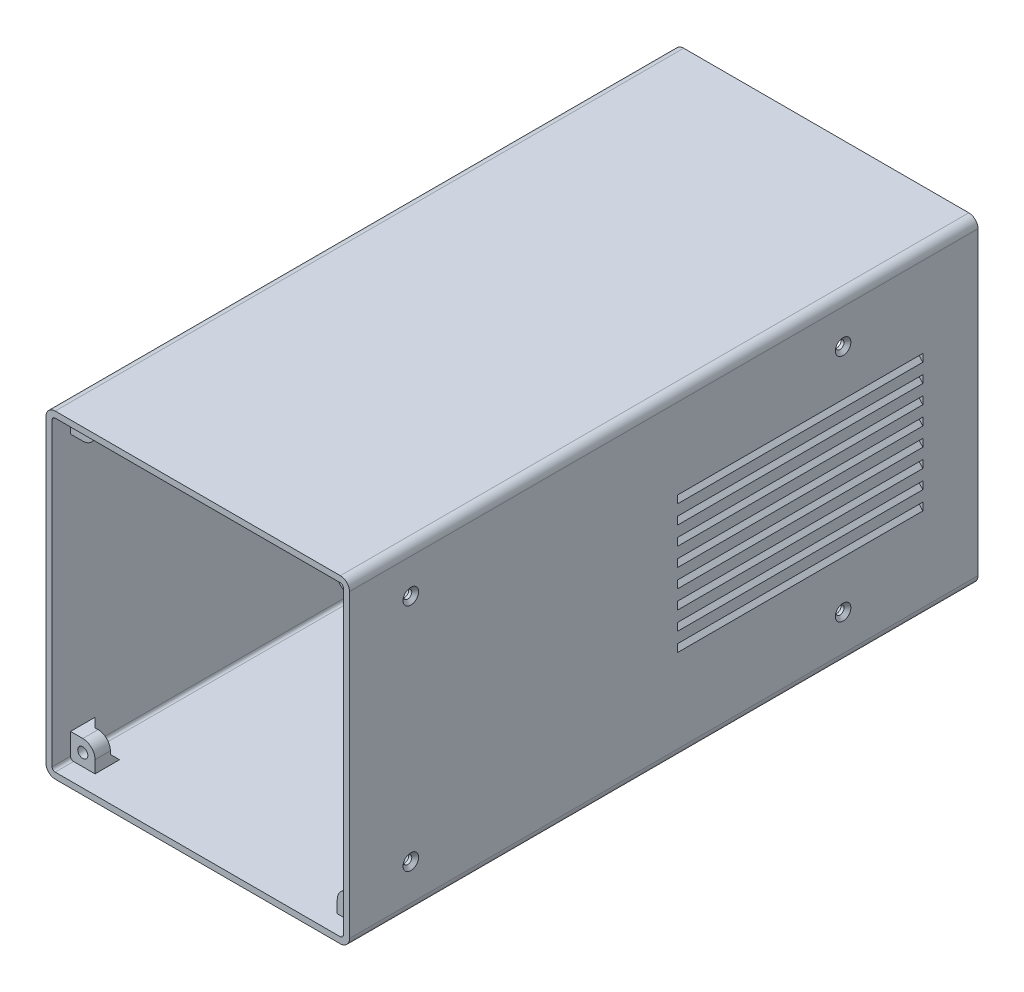
SolidWorks part; units mm, degrees
ref_plane "前视基准面" through (0, 0, 0) normal (0, 0, 1) x (1, 0, 0)
ref_plane "上视基准面" through (0, 0, 0) normal (0, 1, 0) x (1, 0, 0)
ref_plane "右视基准面" through (0, 0, 0) normal (1, 0, 0) x (0, 0, -1)
sketch "草图1" plane through (0, 0, 0) normal (0, 0, 1) x (1, 0, 0)
  line L1 (-46.5, -50) -> (46.5, -50)
  line L2 (-47.5, -49) -> (-47.5, 49)
  line L3 (-46.5, 50) -> (46.5, 50)
  line L4 (47.5, -49) -> (47.5, 49)
  line L5 (-47.5, -50) -> (47.5, 50) construction
  line L6 (-47.5, 50) -> (47.5, -50) construction
  arc A0 (-46.5, -50) -> (-47.5, -49) centre (-46.5, -49) cw
  arc A1 (46.5, -50) -> (47.5, -49) centre (46.5, -49) ccw
  arc A2 (46.5, 50) -> (47.5, 49) centre (46.5, 49) cw
  arc A3 (-47.5, 49) -> (-46.5, 50) centre (-46.5, 49) cw
  point P0 (0, 0)
  dimension "D3" = 1
  dimension "D1" = 100
  dimension "D2" = 95
extrude "凸台-拉伸1" add sketch "草图1" along normal blind 205
shell "抽壳1" thickness 2 removed face at (0, 0, 205) removed face at (0, 0, 0) outward yes
ref_plane "基准面2" through (0, 0, 6) normal (0, 0, -1) x (-1, 0, 0)
ref_plane "基准面3" through (0, 0, 199) normal (0, 0, 1) x (1, 0, 0)
sketch "草图6" plane through (0, 0, 6) normal (0, 0, -1) x (-1, 0, 0)
  line L0 (0, 0) -> (0, 33.2854) construction
  line L1 (-43.5, 42) -> (-47.5, 42)
  line L2 (-39.5, 46) -> (-39.5, 50)
  line L3 (-39.5, 50) -> (-47.5, 50)
  line L4 (-47.5, 42) -> (-47.5, 50)
  line L5 (0, 0) -> (27.226, 0) construction
  line L6 (-46.5, 50) -> (46.5, 50) construction
  line L7 (-47.5, -49) -> (-47.5, 49) construction
  line L8 (39.5, 46) -> (39.5, 50)
  line L9 (43.5, 42) -> (47.5, 42)
  line L10 (47.5, 42) -> (47.5, 50)
  line L11 (39.5, 50) -> (47.5, 50)
  line L12 (39.5, -50) -> (47.5, -50)
  line L13 (47.5, -42) -> (47.5, -50)
  line L14 (43.5, -42) -> (47.5, -42)
  line L15 (39.5, -46) -> (39.5, -50)
  line L16 (-47.5, -42) -> (-47.5, -50)
  line L17 (-39.5, -50) -> (-47.5, -50)
  line L18 (-39.5, -46) -> (-39.5, -50)
  line L19 (-43.5, -42) -> (-47.5, -42)
  arc A0 (-43.5, 42) -> (-39.5, 46) centre (-43.5, 46) ccw
  circle A1 centre (-43.5, 46) radius 1.65
  circle A2 centre (43.5, 46) radius 1.65
  arc A3 (43.5, 42) -> (39.5, 46) centre (43.5, 46) cw
  arc A4 (43.5, -42) -> (39.5, -46) centre (43.5, -46) ccw
  circle A5 centre (43.5, -46) radius 1.65
  circle A6 centre (-43.5, -46) radius 1.65
  arc A7 (-43.5, -42) -> (-39.5, -46) centre (-43.5, -46) cw
  point P15 (-39.5, 42)
  dimension "D3" = 4
  dimension "D4" = 3.3
  dimension "D1" = 8
  dimension "D2" = 8
extrude "凸台-拉伸2" add sketch "草图6" against normal blind 5
sketch "草图7" plane through (0, 0, 199) normal (0, 0, 1) x (1, 0, 0)
  line L0 (-46.5, -50) -> (-39.5, -50) construction
  line L1 (-39.5, -50) -> (-39.5, -46) construction
  line L2 (-43.5, -42) -> (-47.5, -42) construction
  line L3 (-47.5, -42) -> (-47.5, -49) construction
  line L4 (39.5, -50) -> (46.5, -50) construction
  line L5 (47.5, -49) -> (47.5, -42) construction
  line L6 (47.5, -42) -> (43.5, -42) construction
  line L7 (39.5, -46) -> (39.5, -50) construction
  line L8 (46.5, 50) -> (39.5, 50) construction
  line L9 (39.5, 50) -> (39.5, 46) construction
  line L10 (43.5, 42) -> (47.5, 42) construction
  line L11 (47.5, 42) -> (47.5, 49) construction
  line L12 (-39.5, 50) -> (-46.5, 50) construction
  line L13 (-47.5, 49) -> (-47.5, 42) construction
  line L14 (-47.5, 42) -> (-43.5, 42) construction
  line L15 (-39.5, 46) -> (-39.5, 50) construction
  line L16 (-46.5, -50) -> (-39.5, -50)
  line L17 (-39.5, -50) -> (-39.5, -46)
  line L18 (-43.5, -42) -> (-47.5, -42)
  line L19 (-47.5, -42) -> (-47.5, -49)
  line L20 (39.5, -50) -> (46.5, -50)
  line L21 (47.5, -49) -> (47.5, -42)
  line L22 (47.5, -42) -> (43.5, -42)
  line L23 (39.5, -46) -> (39.5, -50)
  line L24 (46.5, 50) -> (39.5, 50)
  line L25 (39.5, 50) -> (39.5, 46)
  line L26 (43.5, 42) -> (47.5, 42)
  line L27 (47.5, 42) -> (47.5, 49)
  line L28 (-39.5, 50) -> (-46.5, 50)
  line L29 (-47.5, 49) -> (-47.5, 42)
  line L30 (-47.5, 42) -> (-43.5, 42)
  line L31 (-39.5, 46) -> (-39.5, 50)
  arc A0 (-47.5, -49) -> (-46.5, -50) centre (-46.5, -49) ccw construction
  arc A1 (-39.5, -46) -> (-43.5, -42) centre (-43.5, -46) ccw construction
  arc A2 (46.5, -50) -> (47.5, -49) centre (46.5, -49) ccw construction
  arc A3 (43.5, -42) -> (39.5, -46) centre (43.5, -46) ccw construction
  arc A4 (47.5, 49) -> (46.5, 50) centre (46.5, 49) ccw construction
  arc A5 (39.5, 46) -> (43.5, 42) centre (43.5, 46) ccw construction
  arc A6 (-46.5, 50) -> (-47.5, 49) centre (-46.5, 49) ccw construction
  arc A7 (-43.5, 42) -> (-39.5, 46) centre (-43.5, 46) ccw construction
  circle A8 centre (43.5, -46) radius 1.65 construction
  circle A9 centre (43.5, 46) radius 1.65 construction
  circle A10 centre (-43.5, 46) radius 1.65 construction
  circle A11 centre (-43.5, -46) radius 1.65 construction
  arc A12 (-47.5, -49) -> (-46.5, -50) centre (-46.5, -49) ccw
  arc A13 (-39.5, -46) -> (-43.5, -42) centre (-43.5, -46) ccw
  arc A14 (46.5, -50) -> (47.5, -49) centre (46.5, -49) ccw
  arc A15 (43.5, -42) -> (39.5, -46) centre (43.5, -46) ccw
  arc A16 (47.5, 49) -> (46.5, 50) centre (46.5, 49) ccw
  arc A17 (39.5, 46) -> (43.5, 42) centre (43.5, 46) ccw
  arc A18 (-46.5, 50) -> (-47.5, 49) centre (-46.5, 49) ccw
  arc A19 (-43.5, 42) -> (-39.5, 46) centre (-43.5, 46) ccw
  circle A20 centre (43.5, -46) radius 1.65
  circle A21 centre (43.5, 46) radius 1.65
  circle A22 centre (-43.5, 46) radius 1.65
  circle A23 centre (-43.5, -46) radius 1.65
extrude "凸台-拉伸3" add sketch "草图7" against normal blind 5
sketch "草图8" plane through (-49.5, 0, 0) normal (-1, 0, 0) x (0, 0, 1)
  line L0 (0, 49) -> (0, -49) construction
  line L1 (96, -43) -> (32, -43) construction
  line L2 (96, -43) -> (96, 43) construction
  line L3 (96, 43) -> (32, 43) construction
  line L4 (32, -43) -> (32, 43) construction
  line L5 (96, -43) -> (32, 43) construction
  line L6 (96, 43) -> (32, -43) construction
  line L7 (100, -46.5) -> (28, -46.5) construction
  line L8 (100, -46.5) -> (100, 46.5) construction
  line L9 (100, 46.5) -> (28, 46.5) construction
  line L10 (28, -46.5) -> (28, 46.5) construction
  line L11 (100, -46.5) -> (28, 46.5) construction
  line L12 (100, 46.5) -> (28, -46.5) construction
  point P0 (64, 0)
  point P5 (64, 0)
  dimension "D1" = 72
  dimension "D2" = 93
  dimension "D3" = 86
  dimension "D4" = 64
  dimension "D5" = 28
hole_wizard "#3 平头机械螺钉的锥形沉头孔 (100)1" positions "草图9" profile "草图10" countersink size "#3" standard "ANSI Inch" end condition up to next
sketch "草图9" plane through (-49.5, 0, 0) normal (-1, 0, 0) x (0, 0, 1)
  point P0 (32, 43)
  point P3 (96, 43)
  point P6 (96, -43)
  point P9 (32, -43)
sketch "草图10" plane through (-49.5, 43, 32) normal (0, 1, 0) x (0, 0, 1)
  line L0 (0, 0) -> (0, 2)
  line L1 (0, 2) -> (1.3208, 2)
  line L2 (1.3208, 2) -> (1.3208, 1.0124)
  line L3 (1.3208, 1.0124) -> (2.5273, 0)
  line L5 (2.5273, 0) -> (0, 0)
  line L6 (-1.3208, 1.0124) -> (-2.5273, 0) construction
  line L11 (0, -6.35) -> (0, 107.95) construction
  dimension "通孔孔直径" = 2.6416
  dimension "通孔孔深度" = 2
  dimension "近端锥形沉头孔直径" = 5.0546
  dimension "近端锥形沉头孔角度" = 100
sketch "草图11" plane through (49.5, 0, 0) normal (1, 0, 0) x (0, 0, -1)
  line L0 (0, -49) -> (0, 49) construction
  line L1 (-40, -46) -> (-190, -46) construction
  line L2 (-40, -46) -> (-40, 46) construction
  line L3 (-40, 46) -> (-190, 46) construction
  line L4 (-190, -46) -> (-190, 46) construction
  line L13 (-194, 50) -> (-11, 50) construction
  line L15 (-185, 37.7) -> (-44, 37.7) construction
  line L16 (-185, 37.7) -> (-185, -37.3) construction
  line L17 (-185, -37.3) -> (-44, -37.3) construction
  line L18 (-44, 37.7) -> (-44, -37.3) construction
  dimension "D1" = 150
  dimension "D2" = 92
  dimension "D3" = 40
  dimension "D4" = 8.7
  dimension "D5" = 4
  dimension "D11" = 4
  dimension "D12" = 141
  dimension "D13" = 75
hole_wizard "#3 平头机械螺钉的锥形沉头孔 (100)2" positions "草图16" profile "草图17" countersink size "#3" standard "ANSI Inch" end condition up to next
sketch "草图16" plane through (49.5, 0, 0) normal (1, 0, 0) x (0, 0, -1)
  point P0 (-185, 37.7)
  point P3 (-44, -37.3)
  point P6 (-185, -37.3)
  point P9 (-44, 37.7)
sketch "草图17" plane through (49.5, 37.7, 185) normal (0, 1, 0) x (0, 0, -1)
  line L0 (0, 0) -> (0, 2)
  line L1 (0, 2) -> (1.3208, 2)
  line L2 (1.3208, 2) -> (1.3208, 1.0124)
  line L3 (1.3208, 1.0124) -> (2.5273, 0)
  line L5 (2.5273, 0) -> (0, 0)
  line L6 (-1.3208, 1.0124) -> (-2.5273, 0) construction
  line L11 (0, -6.35) -> (0, 107.95) construction
  dimension "通孔孔直径" = 2.6416
  dimension "通孔孔深度" = 2
  dimension "近端锥形沉头孔直径" = 5.0546
  dimension "近端锥形沉头孔角度" = 100
ref_plane "基准面1" through (0, 0, 18) normal (0, 0, 1) x (1, 0, 0)
sketch "草图2" plane through (0, 0, 18) normal (0, 0, 1) x (1, 0, 0)
  line L0 (0, 0) -> (0, 60.9493) construction
  line L1 (49.5, 20.2788) -> (47.5, 22.5)
  line L2 (49.5, 20.2788) -> (49.5, 22.7788)
  line L3 (47.5, 22.5) -> (47.5, 25)
  line L4 (49.5, 22.7788) -> (47.5, 25)
  line L5 (49.5, -49) -> (49.5, 49) construction
  line L6 (47.5, -49) -> (47.5, 49) construction
  line L7 (46.5, 50) -> (-46.5, 50) construction
  line L8 (49.5, 16.7788) -> (47.5, 19)
  line L9 (47.5, 16.5) -> (47.5, 19)
  line L10 (49.5, 14.2788) -> (49.5, 16.7788)
  line L11 (49.5, 14.2788) -> (47.5, 16.5)
  line L12 (49.5, 10.7788) -> (47.5, 13)
  line L13 (47.5, 10.5) -> (47.5, 13)
  line L14 (49.5, 8.2788) -> (49.5, 10.7788)
  line L15 (49.5, 8.2788) -> (47.5, 10.5)
  line L16 (49.5, 4.7788) -> (47.5, 7)
  line L17 (47.5, 4.5) -> (47.5, 7)
  line L18 (49.5, 2.2788) -> (49.5, 4.7788)
  line L19 (49.5, 2.2788) -> (47.5, 4.5)
  line L20 (49.5, -1.2212) -> (47.5, 1)
  line L21 (47.5, -1.5) -> (47.5, 1)
  line L22 (49.5, -3.7212) -> (49.5, -1.2212)
  line L23 (49.5, -3.7212) -> (47.5, -1.5)
  line L24 (49.5, -7.2212) -> (47.5, -5)
  line L25 (47.5, -7.5) -> (47.5, -5)
  line L26 (49.5, -9.7212) -> (49.5, -7.2212)
  line L27 (49.5, -9.7212) -> (47.5, -7.5)
  line L28 (49.5, -13.2212) -> (47.5, -11)
  line L29 (47.5, -13.5) -> (47.5, -11)
  line L30 (49.5, -15.7212) -> (49.5, -13.2212)
  line L31 (49.5, -15.7212) -> (47.5, -13.5)
  line L32 (49.5, -19.2212) -> (47.5, -17)
  line L33 (47.5, -19.5) -> (47.5, -17)
  line L34 (49.5, -21.7212) -> (49.5, -19.2212)
  line L35 (49.5, -21.7212) -> (47.5, -19.5)
  line L52 (-49.5, -21.7212) -> (-47.5, -19.5)
  line L53 (-49.5, -21.7212) -> (-49.5, -19.2212)
  line L54 (-47.5, -19.5) -> (-47.5, -17)
  line L55 (-49.5, -19.2212) -> (-47.5, -17)
  line L56 (-49.5, -15.7212) -> (-47.5, -13.5)
  line L57 (-49.5, -15.7212) -> (-49.5, -13.2212)
  line L58 (-47.5, -13.5) -> (-47.5, -11)
  line L59 (-49.5, -13.2212) -> (-47.5, -11)
  line L60 (-49.5, -9.7212) -> (-47.5, -7.5)
  line L61 (-49.5, -9.7212) -> (-49.5, -7.2212)
  line L62 (-47.5, -7.5) -> (-47.5, -5)
  line L63 (-49.5, -7.2212) -> (-47.5, -5)
  line L64 (-49.5, -3.7212) -> (-47.5, -1.5)
  line L65 (-49.5, -3.7212) -> (-49.5, -1.2212)
  line L66 (-47.5, -1.5) -> (-47.5, 1)
  line L67 (-49.5, -1.2212) -> (-47.5, 1)
  line L68 (-49.5, 2.2788) -> (-47.5, 4.5)
  line L69 (-49.5, 2.2788) -> (-49.5, 4.7788)
  line L70 (-47.5, 4.5) -> (-47.5, 7)
  line L71 (-49.5, 4.7788) -> (-47.5, 7)
  line L72 (-49.5, 8.2788) -> (-47.5, 10.5)
  line L73 (-49.5, 8.2788) -> (-49.5, 10.7788)
  line L74 (-47.5, 10.5) -> (-47.5, 13)
  line L75 (-49.5, 10.7788) -> (-47.5, 13)
  line L76 (-49.5, 14.2788) -> (-47.5, 16.5)
  line L77 (-49.5, 14.2788) -> (-49.5, 16.7788)
  line L78 (-47.5, 16.5) -> (-47.5, 19)
  line L79 (-49.5, 16.7788) -> (-47.5, 19)
  line L80 (-49.5, 22.7788) -> (-47.5, 25)
  line L81 (-47.5, 22.5) -> (-47.5, 25)
  line L82 (-49.5, 20.2788) -> (-49.5, 22.7788)
  line L83 (-49.5, 20.2788) -> (-47.5, 22.5)
  dimension "D1" = 42
  dimension "D2" = 2.5
  dimension "D3" = 25
  dimension "D4" = 8
extrude "切除-拉伸1" cut sketch "草图2" along normal blind 80
chamfer "倒角1" distance 3 angle 45 16 edges at (-43, -50, 194) (-47.5, -45.5, 194) (43, -50, 194) (47.5, -45.5, 194) (43, 50, 194) (47.5, 45.5, 194) (-43, 50, 194) (-47.5, 45.5, 194) (47.5, 45.5, 11) (43, 50, 11) (-47.5, 45.5, 11) (-43, 50, 11) (-43, -50, 11) (-47.5, -45.5, 11) (43, -50, 11) (47.5, -45.5, 11) tangent propagation no
sketch "草图14" plane through (0, 0, 11) normal (0, 0, 1) x (1, 0, 0)
  line L1 (-43.5, 49.1754) -> (-46.25, 47.5877)
  line L2 (-46.25, 47.5877) -> (-46.25, 44.4123)
  line L3 (-46.25, 44.4123) -> (-43.5, 42.8246)
  line L4 (-43.5, 42.8246) -> (-40.75, 44.4123)
  line L5 (-40.75, 44.4123) -> (-40.75, 47.5877)
  line L6 (-40.75, 47.5877) -> (-43.5, 49.1754)
  line L7 (43.5, 49.1754) -> (40.75, 47.5877)
  line L8 (40.75, 47.5877) -> (40.75, 44.4123)
  line L9 (40.75, 44.4123) -> (43.5, 42.8246)
  line L10 (43.5, 42.8246) -> (46.25, 44.4123)
  line L11 (46.25, 44.4123) -> (46.25, 47.5877)
  line L12 (46.25, 47.5877) -> (43.5, 49.1754)
  line L13 (43.5, -42.8246) -> (40.75, -44.4123)
  line L14 (40.75, -44.4123) -> (40.75, -47.5877)
  line L15 (40.75, -47.5877) -> (43.5, -49.1754)
  line L16 (43.5, -49.1754) -> (46.25, -47.5877)
  line L17 (46.25, -47.5877) -> (46.25, -44.4123)
  line L18 (46.25, -44.4123) -> (43.5, -42.8246)
  line L19 (-43.5, -42.8246) -> (-46.25, -44.4123)
  line L20 (-46.25, -44.4123) -> (-46.25, -47.5877)
  line L21 (-46.25, -47.5877) -> (-43.5, -49.1754)
  line L22 (-43.5, -49.1754) -> (-40.75, -47.5877)
  line L23 (-40.75, -47.5877) -> (-40.75, -44.4123)
  line L24 (-40.75, -44.4123) -> (-43.5, -42.8246)
  circle A0 centre (-43.5, 46) radius 2.75 construction
  circle A1 centre (43.5, 46) radius 2.75 construction
  circle A2 centre (43.5, -46) radius 2.75 construction
  circle A3 centre (-43.5, -46) radius 2.75 construction
  dimension "D1" = 5.5
extrude "切除-拉伸2" cut sketch "草图14" along normal blind 10 and the other way blind 2
sketch "草图15" plane through (0, 0, 194) normal (0, 0, 1) x (1, 0, 0)
  line L1 (-43.5, 49.1754) -> (-46.25, 47.5877)
  line L2 (-46.25, 47.5877) -> (-46.25, 44.4123)
  line L3 (-46.25, 44.4123) -> (-43.5, 42.8246)
  line L4 (-43.5, 42.8246) -> (-40.75, 44.4123)
  line L5 (-40.75, 44.4123) -> (-40.75, 47.5877)
  line L6 (-40.75, 47.5877) -> (-43.5, 49.1754)
  line L7 (43.5, 49.1754) -> (40.75, 47.5877)
  line L8 (40.75, 47.5877) -> (40.75, 44.4123)
  line L9 (40.75, 44.4123) -> (43.5, 42.8246)
  line L10 (43.5, 42.8246) -> (46.25, 44.4123)
  line L11 (46.25, 44.4123) -> (46.25, 47.5877)
  line L12 (46.25, 47.5877) -> (43.5, 49.1754)
  line L13 (43.5, -42.8246) -> (40.75, -44.4123)
  line L14 (40.75, -44.4123) -> (40.75, -47.5877)
  line L15 (40.75, -47.5877) -> (43.5, -49.1754)
  line L16 (43.5, -49.1754) -> (46.25, -47.5877)
  line L17 (46.25, -47.5877) -> (46.25, -44.4123)
  line L18 (46.25, -44.4123) -> (43.5, -42.8246)
  line L19 (-43.5, -42.8246) -> (-46.25, -44.4123)
  line L20 (-46.25, -44.4123) -> (-46.25, -47.5877)
  line L21 (-46.25, -47.5877) -> (-43.5, -49.1754)
  line L22 (-43.5, -49.1754) -> (-40.75, -47.5877)
  line L23 (-40.75, -47.5877) -> (-40.75, -44.4123)
  line L24 (-40.75, -44.4123) -> (-43.5, -42.8246)
  circle A0 centre (-43.5, 46) radius 2.75 construction
  circle A1 centre (43.5, 46) radius 2.75 construction
  circle A2 centre (43.5, -46) radius 2.75 construction
  circle A3 centre (-43.5, -46) radius 2.75 construction
  dimension "D1" = 5.5
extrude "切除-拉伸3" cut sketch "草图15" against normal blind 10 and the other way blind 2
